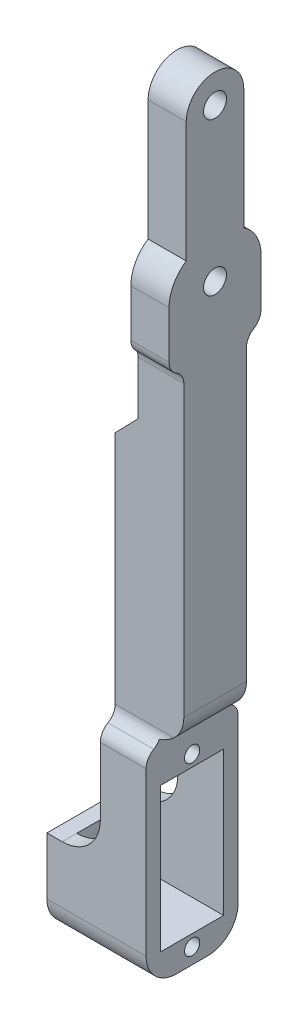
SolidWorks part; units mm, degrees
ref_plane "前视基准面" through (0, 0, 0) normal (0, 0, 1) x (1, 0, 0)
ref_plane "上视基准面" through (0, 0, 0) normal (0, 1, 0) x (1, 0, 0)
ref_plane "右视基准面" through (0, 0, 0) normal (1, 0, 0) x (0, 0, -1)
sketch "Sketch1" plane through (0, 0, 0) normal (1, 0, 0) x (0, 0, -1)
  circle A0 centre (2.9834, 10.8268) radius 7.75 construction
  circle A1 centre (2.9834, 10.8268) radius 6.25 construction
  circle A2 centre (2.9834, 18.5768) radius 0.8
  circle A3 centre (2.9834, 3.0768) radius 0.8
  circle A4 centre (-3.2666, 10.8268) radius 0.8
  circle A5 centre (9.2334, 10.8268) radius 0.8
  circle A6 centre (2.9834, 10.8268) radius 10
  circle A7 centre (2.9834, 10.8268) radius 3.3018
  dimension "D1" = 15.5
  dimension "D2" = 12.5
  dimension "D3" = 20
extrude "Boss-Extrude1" add sketch "Sketch1" along normal blind 1.5
sketch "Sketch2" plane through (0, 0, 0) normal (-1, 0, 0) x (0, 0, 1)
  line L0 (-2.9834, 10.8268) -> (-2.9834, 25.4318) construction
  line L2 (-12.9834, 90.8268) -> (7.0166, 90.8268) construction
  line L3 (-12.9834, 90.8268) -> (-12.9834, 10.8268) construction
  line L4 (-12.9834, 10.8268) -> (7.0166, 10.8268) construction
  line L5 (7.0166, 90.8268) -> (7.0166, 10.8268) construction
  line L6 (-12.9834, 90.8268) -> (7.0166, 10.8268) construction
  line L7 (-12.9834, 10.8268) -> (7.0166, 90.8268) construction
  line L8 (-15.5319, 90.8268) -> (9.5652, 90.8268)
  line L9 (-15.5319, 90.8268) -> (-15.5319, 10.8268)
  line L10 (-15.5319, 10.8268) -> (9.5652, 10.8268) construction
  line L11 (9.5652, 90.8268) -> (9.5652, 10.8268)
  line L12 (-15.5319, 90.8268) -> (9.5652, 10.8268) construction
  line L13 (-15.5319, 10.8268) -> (9.5652, 90.8268) construction
  circle A0 centre (-2.9834, 10.8268) radius 10 construction
  arc A1 (-12.9834, 10.8268) -> (7.0166, 10.8268) centre (-2.9834, 10.8268) cw construction
  circle A2 centre (-2.9834, 10.8268) radius 12.5485 construction
  circle A3 centre (-2.9834, 10.8268) radius 10
  arc A4 (-15.5319, 10.8268) -> (9.5652, 10.8268) centre (-2.9834, 10.8268) ccw
  circle A5 centre (-2.9834, 10.8268) radius 0.6321 construction
  point P1 (-2.9834, 50.8268)
  point P12 (-2.9834, 50.8268)
  dimension "D1" = 0
  dimension "D2" = 80
extrude "Boss-Extrude2" add sketch "Sketch2" against normal blind 9
sketch "Sketch3" plane through (9, 0, 0) normal (1, 0, 0) x (0, 0, -1)
  line L0 (2.9834, 95.8916) -> (2.9834, 22.8694) construction
  line L1 (-9.5652, 90.8268) -> (15.5319, 90.8268) construction
  line L3 (-3.0511, 36.1504) -> (-3.0511, 97.5726)
  line L4 (-3.0511, 97.5726) -> (-16.389, 97.5726)
  line L5 (-16.389, 97.5726) -> (-16.389, 8.1411)
  line L6 (-16.389, 8.1411) -> (-9.5652, 10.8268)
  line L7 (22.3558, 8.1411) -> (15.5319, 10.8268)
  line L8 (22.3558, 97.5726) -> (22.3558, 8.1411)
  line L9 (9.0179, 97.5726) -> (22.3558, 97.5726)
  line L10 (9.0179, 36.1504) -> (9.0179, 97.5726)
  circle A0 centre (2.9834, 85.8268) radius 1.5
  spline S0 degree 3 poles (-9.5652, 10.8268) (-9.6442, 15.1222) (-6.9162, 23.507) (-3.4283, 31.5617) (-3.0511, 36.1504) knots 0 0 0 0 0.482385 1 1 1 1
  spline S1 degree 3 poles (15.5319, 10.8268) (15.611, 15.1222) (12.883, 23.507) (9.395, 31.5617) (9.0179, 36.1504) knots 0 0 0 0 0.482385 1 1 1 1
  dimension "D1" = 5
extrude "Cut-Extrude1" cut sketch "Sketch3" against normal through all both and the other way through all
fillet "Fillet1" radius 5 2 edges at (4.5, 90.8268, -9.0179) (4.5, 90.8268, 3.0511)
sketch "Sketch4" plane through (9, 0, 0) normal (1, 0, 0) x (0, 0, -1)
  line L0 (2.9834, 85.8268) -> (2.9834, 105.8268) construction
  line L1 (-0.7887, 85.8268) -> (-0.7887, 105.8268)
  line L2 (6.7554, 85.8268) -> (6.7554, 105.8268)
  arc A0 (-0.7887, 85.8268) -> (6.7554, 85.8268) centre (2.9834, 85.8268) ccw
  arc A1 (6.7554, 105.8268) -> (-0.7887, 105.8268) centre (2.9834, 105.8268) ccw
  circle A2 centre (2.9834, 105.8268) radius 1.5
  circle A3 centre (2.9834, 85.8268) radius 1.5
  point P3 (2.9834, 95.8268)
  dimension "D1" = 20
extrude "Boss-Extrude3" add sketch "Sketch4" against normal blind 5
sketch "Sketch5" plane through (0, 0, 0) normal (-1, 0, 0) x (0, 0, 1)
  line L0 (3.0511, 66.6904) -> (-0.5206, 90.6184)
  line L1 (3.0511, 36.1504) -> (3.0511, 85.8268) construction
  line L2 (-0.5206, 90.6184) -> (8.9944, 90.6184)
  line L3 (8.9944, 90.6184) -> (4.4528, 66.6904)
  line L4 (4.4528, 66.6904) -> (3.0511, 66.6904)
  line L5 (-9.0179, 66.6904) -> (-5.4462, 90.6184)
  line L6 (-9.0179, 85.8268) -> (-9.0179, 36.1504) construction
  line L7 (-5.4462, 90.6184) -> (-12.4698, 95.2806)
  line L8 (-12.4698, 95.2806) -> (-31.4476, 66.6904)
  line L9 (-31.4476, 66.6904) -> (-9.0179, 66.6904)
  arc A0 (0.7887, 90.0108) -> (-1.9489, 90.8268) centre (-1.9489, 85.8268) ccw construction
  arc A1 (-4.0179, 90.8268) -> (-6.7554, 90.0108) centre (-4.0179, 85.8268) ccw construction
  dimension "D1" = 0
extrude "Cut-Extrude2" cut sketch "Sketch5" against normal up to surface (4 mm away) up to face at (4, 96.25, -2.9834)
fillet "Fillet3" radius 2 2 edges at (2, 90.6184, -5.4462) (2, 90.6184, -0.5206)
sketch "Sketch6" plane through (9, 0, 0) normal (1, 0, 0) x (0, 0, -1)
  line L0 (9.0179, 36.1504) -> (9.0179, 28.2815) construction
  line L2 (-3.0511, 36.1504) -> (9.0179, 36.1504)
  line L3 (-3.0511, 36.1504) -> (-3.0511, 0)
  line L4 (-3.0511, 0) -> (9.0179, 0)
  line L5 (9.0179, 36.1504) -> (9.0179, 0)
extrude "Boss-Extrude4" add sketch "Sketch6" against normal up to surface (9 mm away) up to face at (0, 85.8268, -4.4834)
sketch "Sketch7" plane through (9, 0, 0) normal (1, 0, 0) x (0, 0, -1)
  line L0 (-3.0511, 36.1504) -> (-3.0511, -1.9848) construction
  line L1 (-3.0511, -1.9848) -> (-23.4996, -1.9848)
  line L2 (-23.4996, -1.9848) -> (-3.0511, 36.1504)
  line L3 (9.0179, 36.1504) -> (9.0179, -7.6597) construction
  line L4 (9.0179, -7.6597) -> (33.092, 2.7443)
  line L5 (33.092, 2.7443) -> (9.0179, 36.1504)
  line L6 (-3.0511, 36.1504) -> (-3.0511, 6.6932)
  line L7 (-3.0511, 6.6932) -> (9.0179, 6.6932)
  line L8 (9.0179, 6.6932) -> (9.0179, 36.1504)
  line L9 (-3.0511, -1.9848) -> (9.0179, -7.6597)
extrude "Cut-Extrude3" cut sketch "Sketch7" against normal through all both and the other way through all
sketch "Sketch8" plane through (9, 0, 0) normal (1, 0, 0) x (0, 0, -1)
  line L0 (2.9834, 88.9737) -> (2.9834, 82.9384) construction
  line L1 (-3.0511, 6.6932) -> (9.0179, 6.6932) construction
  line L2 (7.1084, 29.1432) -> (-1.1416, 29.1432)
  line L3 (7.1084, 29.1432) -> (7.1084, 10.2432)
  line L4 (7.1084, 10.2432) -> (-1.1416, 10.2432)
  line L5 (-1.1416, 29.1432) -> (-1.1416, 10.2432)
  line L6 (7.1084, 29.1432) -> (-1.1416, 10.2432) construction
  line L7 (7.1084, 10.2432) -> (-1.1416, 29.1432) construction
  line L8 (3.7847, 30.6482) -> (2.1821, 30.6482) construction
  line L9 (3.7847, 30.6482) -> (3.7847, 8.7382) construction
  line L10 (3.7847, 8.7382) -> (2.1821, 8.7382) construction
  line L11 (2.1821, 30.6482) -> (2.1821, 8.7382) construction
  line L12 (3.7847, 30.6482) -> (2.1821, 8.7382) construction
  line L13 (3.7847, 8.7382) -> (2.1821, 30.6482) construction
  circle A0 centre (2.9834, 30.6482) radius 1
  circle A1 centre (2.9834, 8.7382) radius 1
  circle A2 centre (2.9834, 85.8268) radius 0.5708 construction
  point P1 (2.9834, 19.6932)
  point P8 (2.9834, 19.6932)
  dimension "D4" = 13
  dimension "D1" = 8.25
  dimension "D2" = 18.9
  dimension "D3" = 21.91
  dimension "D5" = 0
  dimension "D6" = 0
extrude "Cut-Extrude4" cut sketch "Sketch8" against normal through all both and the other way through all
fillet "Fillet4" radius 4 2 edges at (4.5, 6.6932, -9.0179) (4.5, 6.6932, 3.0511)
sketch "Sketch9" plane through (9, 0, 0) normal (1, 0, 0) x (0, 0, -1)
  line L1 (-8.9789, -0.9142) -> (15.4035, -0.9142)
  line L2 (-8.9789, -0.9142) -> (-8.9789, 34.4574)
  line L3 (-8.9789, 34.4574) -> (15.4035, 34.4574)
  line L4 (15.4035, -0.9142) -> (15.4035, 34.4574)
extrude "Cut-Extrude5" cut sketch "Sketch9" against normal blind 3
fillet "Fillet5" radius 4 1 edges at (9, 34.4574, -2.9834)
sketch "Sketch10" plane through (0, 0, 0) normal (-1, 0, 0) x (0, 0, 1)
  circle A0 centre (-2.9834, 85.8268) radius 20.0653
extrude "Cut-Extrude6" cut sketch "Sketch10" against normal blind 3
sketch "Sketch11" plane through (0, 0, 0) normal (-1, 0, 0) x (0, 0, 1)
  line L0 (-3.0031, 100.8499) -> (-3.0031, 107.7727) construction
  line L1 (-9.0179, 76.2586) -> (-9.0179, 35.3573) construction
  line L2 (-7.11, 76.2586) -> (-7.11, 35.3573)
  line L3 (-10.9258, 76.2586) -> (-10.9258, 35.3573)
  line L4 (-9.0179, 66.6904) -> (-9.0179, 10.6932) construction
  line L5 (-9.0179, 66.6904) -> (-9.0179, 85.8268) construction
  line L6 (3.0116, 76.2586) -> (3.0116, 35.3573) construction
  line L7 (1.1037, 76.2586) -> (1.1037, 35.3573)
  line L8 (4.9195, 76.2586) -> (4.9195, 35.3573)
  arc A0 (-7.11, 76.2586) -> (-10.9258, 76.2586) centre (-9.0179, 76.2586) ccw
  arc A1 (-10.9258, 35.3573) -> (-7.11, 35.3573) centre (-9.0179, 35.3573) ccw
  arc A2 (1.1037, 76.2586) -> (4.9195, 76.2586) centre (3.0116, 76.2586) cw
  arc A3 (4.9195, 35.3573) -> (1.1037, 35.3573) centre (3.0116, 35.3573) cw
  point P5 (-9.0179, 55.8079)
  point P19 (3.0116, 55.8079)
extrude "Cut-Extrude7" cut sketch "Sketch11" against normal through all both and the other way through all
fillet "Fillet6" radius 2 4 edges at (3, 33.4494, -9.0179) (3, 33.4498, 3.0511) (6.5, 78.1665, -9.0179) (6.5, 78.1661, 3.0511)
chamfer "Chamfer1" distance 3 angle 45 1 edges at (3, 65.7614, -3.0035)
sketch "Sketch12" plane through (0, 0, 0) normal (-1, 0, 0) x (0, 0, 1)
  line L0 (-5.0179, 6.6932) -> (-0.9489, 6.6932) construction
  line L1 (-5.0179, 6.6932) -> (-0.9489, 6.6932)
  line L2 (-9.0179, 10.6932) -> (-9.0179, 18.199)
  line L3 (-9.0179, 32) -> (-9.0179, 10.6932) construction
  line L4 (-9.0179, 18.199) -> (3.0511, 18.199)
  line L5 (3.0511, 10.6932) -> (3.0511, 31.9768) construction
  line L6 (3.0511, 18.199) -> (3.0511, 10.6932)
  arc A0 (-9.0179, 10.6932) -> (-5.0179, 6.6932) centre (-5.0179, 10.6932) ccw construction
  arc A1 (-9.0179, 10.6932) -> (-5.0179, 6.6932) centre (-5.0179, 10.6932) ccw
  arc A2 (-0.9489, 6.6932) -> (3.0511, 10.6932) centre (-0.9489, 10.6932) ccw construction
  arc A3 (-0.9489, 6.6932) -> (3.0511, 10.6932) centre (-0.9489, 10.6932) ccw
  circle A4 centre (-2.9834, 8.7382) radius 1 construction
  circle A5 centre (-2.9834, 8.7382) radius 1
  circle A6 centre (-2.9834, 15.7382) radius 1
  dimension "D1" = 7
extrude "Boss-Extrude5" add sketch "Sketch12" along normal blind 7
sketch "Sketch13" plane through (0, 0, 0) normal (1, 0, 0) x (0, 0, -1)
  line L1 (-1.1416, 18.199) -> (7.1084, 18.199)
  line L2 (-1.1416, 18.199) -> (-1.1416, 10.2432)
  line L3 (-1.1416, 10.2432) -> (7.1084, 10.2432)
  line L4 (7.1084, 18.199) -> (7.1084, 10.2432)
extrude "Cut-Extrude8" cut sketch "Sketch13" against normal offset from surface (5 mm away) 2 up to face at (-7, 8.7382, -1.9834)
fillet "Fillet7" radius 5 2 edges at (0, 18.199, -8.0631) (0, 18.199, 2.0964)
sketch "Sketch14" plane through (0, 0, 0) normal (-1, 0, 0) x (0, 0, 1)
  line L0 (-7.1084, 29.1432) -> (1.1416, 29.1432) construction
  line L1 (-4.3536, 29.1432) -> (-1.7598, 29.1432)
  line L2 (-4.3536, 29.1432) -> (-4.3536, 84.3202)
  line L3 (-4.3536, 84.3202) -> (-1.7598, 84.3202)
  line L4 (-1.7598, 29.1432) -> (-1.7598, 84.3202)
extrude "Cut-Extrude9" cut sketch "Sketch14" against normal blind 2.5
